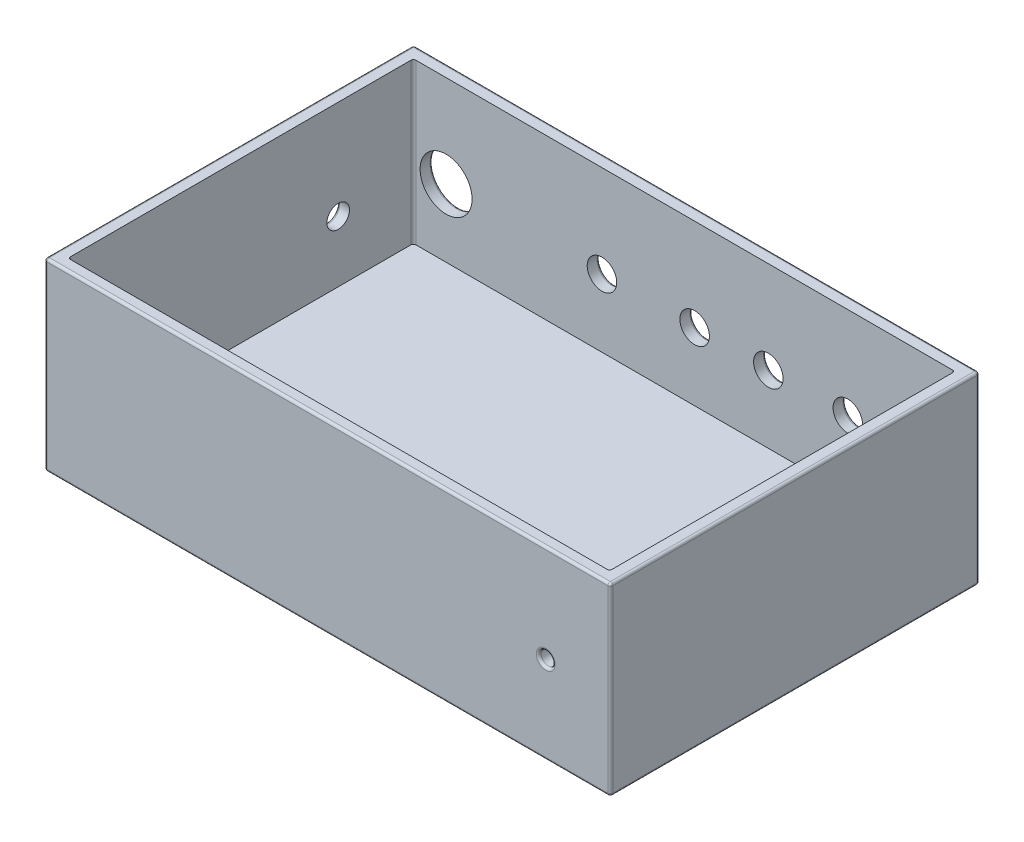
SolidWorks part; units mm, degrees
ref_plane "Front Plane" through (0, 0, 0) normal (0, 0, 1) x (1, 0, 0)
ref_plane "Top Plane" through (0, 0, 0) normal (0, 1, 0) x (1, 0, 0)
ref_plane "Right Plane" through (0, 0, 0) normal (1, 0, 0) x (0, 0, -1)
sketch "Sketch1" plane through (0, 0, 0) normal (0, 1, 0) x (1, 0, 0)
  line L1 (0, 0) -> (230, 0)
  line L2 (0, 0) -> (0, 150)
  line L3 (0, 150) -> (230, 150)
  line L4 (230, 0) -> (230, 150)
  line L5 (0, 0) -> (230, 150) construction
  line L6 (0, 150) -> (230, 0) construction
  point P4 (115, 75)
extrude "Boss-Extrude8" add sketch "Sketch1" along normal blind 10
sketch "Sketch7" plane through (0, 10, 0) normal (0, 1, 0) x (1, 0, 0)
  line L0 (0, 150) -> (230, 150)
  line L1 (0, 150) -> (0, 0)
  line L2 (230, 150) -> (230, 0)
  line L3 (0, 0) -> (230, 0)
  line L5 (4.9522, 144.9735) -> (225.0478, 144.9735)
  line L6 (4.9522, 144.9735) -> (4.9522, 4.6182)
  line L7 (4.9522, 4.6182) -> (225.0478, 4.6182)
  line L8 (225.0478, 144.9735) -> (225.0478, 4.6182)
  line L9 (115, 4.6182) -> (115, 144.9735) construction
  line L10 (4.9522, 74.7958) -> (225.0478, 74.7958) construction
  point P0 (115, 74.7958)
extrude "Boss-Extrude9" add sketch "Sketch7" along normal blind 65
fillet "Fillet5" radius 1 4 edges at (0, 37.5, 0) (0, 37.5, -150) (230, 37.5, 0) (230, 37.5, -150)
fillet "Fillet6" radius 1 1 edges at (4.9522, 42.5, -144.9735)
fillet "Fillet7" radius 1 1 edges at (225.0478, 42.5, -4.6182)
fillet "Fillet8" radius 1 1 edges at (225.0478, 42.5, -144.9735)
fillet "Fillet9" radius 1 1 edges at (4.9522, 42.5, -4.6182)
sketch "Sketch8" plane through (0, 0, -150) normal (0, 0, -1) x (-1, 0, 0)
  circle A0 centre (-18.2282, 37.5) radius 10.5639
  circle A4 centre (-119.2548, 37.5) radius 10
  circle A5 centre (-81.5912, 37.5) radius 10
  circle A6 centre (-213.6911, 37.5) radius 10
  circle A7 centre (-181.5221, 37.5) radius 10
  circle A8 centre (-149.2195, 37.5) radius 10
sketch "Sketch11" plane through (0, 0, -150) normal (0, 0, -1) x (-1, 0, 0)
  circle A1 centre (-213.6911, 37.5) radius 6
  circle A2 centre (-181.5221, 37.5) radius 6
  circle A3 centre (-149.2195, 37.5) radius 6
  circle A4 centre (-119.2548, 37.5) radius 6
  circle A5 centre (-81.5912, 37.5) radius 6
extrude "Cut-Extrude1" cut sketch "Sketch11" against normal blind 10 contours A3 | A1 | A2 | A5 | A4
extrude "Cut-Extrude2" cut sketch "Sketch8" against normal blind 10 contours A0
sketch "Sketch12" plane through (0, 0, 0) normal (-1, 0, 0) x (0, 0, 1)
  circle A0 centre (-114.3975, 34.8225) radius 4.59
extrude "Cut-Extrude4" cut sketch "Sketch12" against normal blind 10
sketch "Sketch13" plane through (0, 0, 0) normal (0, 0, 1) x (1, 0, 0)
  circle A0 centre (203.6977, 35.4796) radius 2.848
extrude "Cut-Extrude5" cut sketch "Sketch13" against normal blind 10
fillet "Fillet1" radius 1 17 edges at (0, 75, -75) (0, 0, -75) (0.2929, 75, -149.7071) (115, 75, -150) (229.7071, 75, -149.7071) (230, 75, -75) (229.7071, 75, -0.2929) (115, 75, 0) (0.2929, 75, -0.2929) (0.2929, 0, -149.7071) (115, 0, -150) (229.7071, 0, -149.7071) (230, 0, -75) (229.7071, 0, -0.2929) (115, 0, 0) (0.2929, 0, -0.2929) (0, 34.8225, -109.8075)
fillet "Fillet2" radius 1 1 edges at (206.5457, 35.4796, 0)
fillet "Fillet3" radius 1 rebuild error yes
fillet "Fillet4" radius 1 6 edges at (143.2195, 37.5, -150) (207.6911, 37.5, -150) (175.5221, 37.5, -150) (75.5912, 37.5, -150) (113.2548, 37.5, -150) (7.6643, 37.5, -150)
